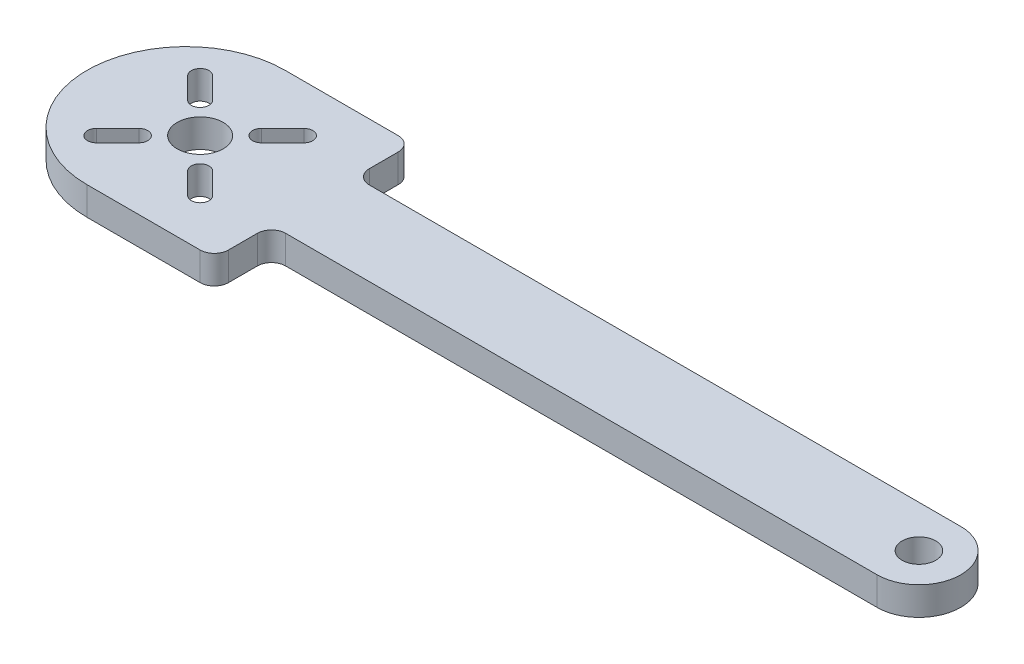
SolidWorks part; units mm, degrees
material "Thornel VCB-20 Carbon Cloth"
ref_plane "Front Plane" through (0, 0, 0) normal (0, 0, 1) x (1, 0, 0)
ref_plane "Top Plane" through (0, 0, 0) normal (0, 1, 0) x (1, 0, 0)
ref_plane "Right Plane" through (0, 0, 0) normal (1, 0, 0) x (0, 0, -1)
sketch "Sketch1" plane through (0, 0, 0) normal (0, 1, 0) x (1, 0, 0)
  line L0 (-58.0134, 7.2134) -> (-43.5866, -7.2134) construction
  line L1 (-50.8, 14) -> (-36.8, 14)
  line L2 (-50.8, 14) -> (-50.8, -14) construction
  line L3 (-50.8, -14) -> (-36.8, -14)
  line L7 (-58.4887, -7.6887) -> (-43.1113, 7.6887) construction
  line L8 (-58.1362, 7.3362) -> (-55.131, 4.331) construction
  line L9 (-57.2523, 8.2201) -> (-54.2471, 5.2149)
  line L10 (-59.0201, 6.4523) -> (-56.0149, 3.4471)
  line L11 (-43.4638, 7.3362) -> (-46.469, 4.331) construction
  line L12 (-42.5799, 6.4523) -> (-45.5851, 3.4471)
  line L13 (-44.3477, 8.2201) -> (-47.3529, 5.2149)
  line L14 (-43.4638, -7.3362) -> (-46.469, -4.331) construction
  line L15 (-44.3477, -8.2201) -> (-47.3529, -5.2149)
  line L16 (-42.5799, -6.4523) -> (-45.5851, -3.4471)
  line L17 (-58.1362, -7.3362) -> (-55.131, -4.331) construction
  line L18 (-59.0201, -6.4523) -> (-56.0149, -3.4471)
  line L19 (-57.2523, -8.2201) -> (-54.2471, -5.2149)
  line L21 (-34.8, 7.9146) -> (-34.8, 12)
  line L24 (-34.8, -12) -> (-34.8, -7.9146)
  line L32 (-32.8, 5.9146) -> (50.8, 5.9146)
  line L33 (-32.8, -5.9146) -> (50.8, -5.9146)
  line L34 (-50.8, 0) -> (50.8, 0) construction
  line L35 (-50.8, 14) -> (-52.8, 14)
  line L36 (-50.8, -14) -> (-52.8, -14)
  circle A2 centre (-50.8, 0) radius 3.25
  arc A3 (-57.2523, 8.2201) -> (-59.0201, 6.4523) centre (-58.1362, 7.3362) ccw
  arc A4 (-56.0149, 3.4471) -> (-54.2471, 5.2149) centre (-55.131, 4.331) ccw
  arc A5 (-42.5799, 6.4523) -> (-44.3477, 8.2201) centre (-43.4638, 7.3362) ccw
  arc A6 (-47.3529, 5.2149) -> (-45.5851, 3.4471) centre (-46.469, 4.331) ccw
  arc A7 (-44.3477, -8.2201) -> (-42.5799, -6.4523) centre (-43.4638, -7.3362) ccw
  arc A8 (-45.5851, -3.4471) -> (-47.3529, -5.2149) centre (-46.469, -4.331) ccw
  arc A9 (-59.0201, -6.4523) -> (-57.2523, -8.2201) centre (-58.1362, -7.3362) ccw
  arc A10 (-54.2471, -5.2149) -> (-56.0149, -3.4471) centre (-55.131, -4.331) ccw
  circle A11 centre (50.8, 0) radius 2.3813
  arc A12 (-34.8, -7.9146) -> (-32.8, -5.9146) centre (-32.8, -7.9146) cw
  arc A13 (-32.8, 5.9146) -> (-34.8, 7.9146) centre (-32.8, 7.9146) cw
  arc A14 (-36.8, -14) -> (-34.8, -12) centre (-36.8, -12) ccw
  arc A15 (-34.8, 12) -> (-36.8, 14) centre (-36.8, 12) ccw
  arc A16 (50.8, 5.9146) -> (50.8, -5.9146) centre (50.8, 0) cw
  arc A17 (-52.8, -14) -> (-52.8, 14) centre (-52.8, 0) cw
  point P0 (0, 0)
  point P12 (-50.8, 0)
  point P14 (-50.8, 0)
  point P17 (-56.6336, 5.8336)
  point P27 (-44.9664, 5.8336)
  point P34 (-44.9664, -5.8336)
  point P41 (-56.6336, -5.8336)
  point P46 (-50.8, 0)
  point P53 (-34.8, -7)
  point P56 (-34.8, 7)
  point P59 (-34.8, -14)
  point P62 (-34.8, 14)
  point P64 (0, 0)
  dimension "D3" = 6.5
  dimension "D6" = 8.25
  dimension "D10" = 4.7625
  dimension "D17" = 2
  dimension "D18" = 2
  dimension "D16" = 5.9146
  dimension "D2" = 14
  dimension "D4" = 45
  dimension "D5" = 45
  dimension "D7" = 4.25
  dimension "D8" = 2.5
  dimension "D11" = 16
  dimension "D12" = 16
  dimension "D13" = 7
  dimension "D14" = 7
  dimension "D15" = 101.6
  dimension "D19" = 50.8
  dimension "D20" = 2
  dimension "D9" = 4
extrude "Boss-Extrude1" add sketch "Sketch1" along normal blind 4
